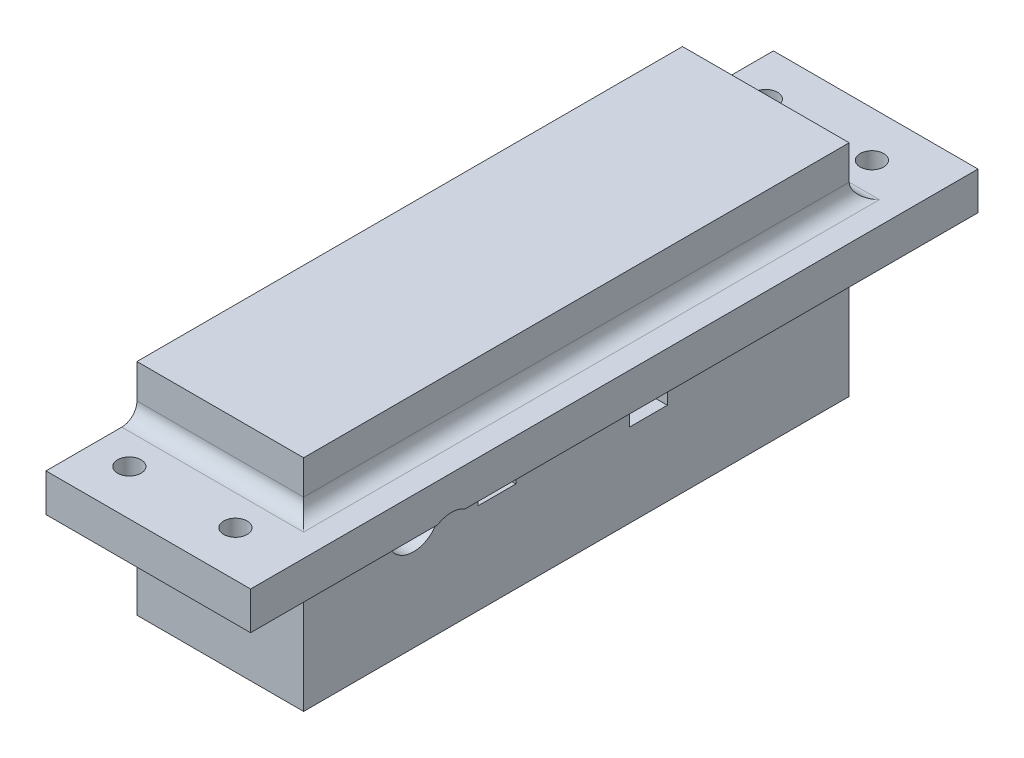
SolidWorks part; units mm, degrees
ref_plane "前基準面" through (0, 0, 0) normal (0, 0, 1) x (1, 0, 0)
ref_plane "上基準面" through (0, 0, 0) normal (0, 1, 0) x (1, 0, 0)
ref_plane "右基準面" through (0, 0, 0) normal (1, 0, 0) x (0, 0, -1)
sketch "草圖1" plane through (0, 0, 0) normal (1, 0, 0) x (0, 0, -1)
  line L1 (-30, 11.5) -> (33, 11.5)
  line L2 (-33, 8.5) -> (-33, -8.5)
  line L3 (-30, -11.5) -> (33, -11.5)
  line L4 (33, 11.5) -> (33, -11.5)
  line L5 (-33, 11.5) -> (33, -11.5) construction
  line L6 (-33, -11.5) -> (33, 11.5) construction
  line L7 (-36, 14.5) -> (36, 14.5)
  line L8 (-36, 14.5) -> (-36, -14.5)
  line L9 (-36, -14.5) -> (36, -14.5)
  line L10 (36, 14.5) -> (36, -14.5)
  line L11 (-36, 14.5) -> (36, -14.5) construction
  line L12 (-36, -14.5) -> (36, 14.5) construction
  arc A0 (-33, -8.5) -> (-30, -11.5) centre (-30, -8.5) ccw
  arc A1 (-30, 11.5) -> (-33, 8.5) centre (-30, 8.5) ccw
  point P0 (0, 0)
  point P6 (0, 0)
  dimension "D5" = 3
  dimension "D1" = 23
  dimension "D2" = 66
  dimension "D3" = 3
  dimension "D4" = 3
extrude "填料-伸長1" add sketch "草圖1" along normal blind 20
sketch "草圖2" plane through (0, 0, 36) normal (0, 0, 1) x (1, 0, 0)
  line L0 (0, 0) -> (20, 0) construction
  line L1 (0, 14.5) -> (0, -14.5) construction
  line L2 (20, 14.5) -> (20, -14.5) construction
  line L4 (0, 3) -> (11, 3)
  line L5 (0, 3) -> (0, -3)
  line L6 (0, -3) -> (11, -3)
  line L7 (11, 3) -> (11, -3)
  dimension "D1" = 11
  dimension "D2" = 3
  dimension "D3" = 3
extrude "除料-伸長1" cut sketch "草圖2" against normal up to next
sketch "草圖3" plane through (0, 0, -36) normal (0, 0, -1) x (-1, 0, 0)
  line L0 (0, 0) -> (-20, 0) construction
  line L1 (0, -14.5) -> (0, 14.5) construction
  line L2 (-20, -14.5) -> (-20, 14.5) construction
  circle A0 centre (-10, 0) radius 1.5
  dimension "D1" = 3
extrude "除料-伸長2" cut sketch "草圖3" against normal up to next
sketch "草圖4" plane through (20, 0, 0) normal (1, 0, 0) x (0, 0, -1)
  line L0 (-36, -14.5) -> (36, -14.5) construction
  line L1 (-36, 14.5) -> (36, 14.5)
  line L2 (-36, 14.5) -> (-36, -14.5)
  line L3 (-36, -14.5) -> (36, -14.5)
  line L4 (36, 14.5) -> (36, -14.5)
  line L5 (0, 0) -> (-36, 0) construction
  line L6 (-25, 3.5) -> (-18, 3.5) construction
  line L7 (-25, 3.5) -> (-25, -3.5) construction
  line L8 (-25, -3.5) -> (-18, -3.5) construction
  line L9 (-18, 3.5) -> (-18, -3.5) construction
  line L10 (-25, 3.5) -> (-18, -3.5) construction
  line L11 (-25, -3.5) -> (-18, 3.5) construction
  line L14 (36, -14.5) -> (36, 14.5) construction
  line L15 (-33, 8.5) -> (-33, -8.5) construction
  line L16 (-13, 2.5) -> (-8, 2.5)
  line L17 (-13, 2.5) -> (-13, -2.5)
  line L18 (-13, -2.5) -> (-8, -2.5)
  line L19 (-8, 2.5) -> (-8, -2.5)
  line L20 (-13, 2.5) -> (-8, -2.5) construction
  line L21 (-13, -2.5) -> (-8, 2.5) construction
  line L22 (0, 0) -> (36, 0) construction
  line L23 (7, 3.5) -> (12, 3.5)
  line L24 (7, 3.5) -> (7, -3.5)
  line L25 (7, -3.5) -> (12, -3.5)
  line L26 (12, 3.5) -> (12, -3.5)
  line L27 (7, 3.5) -> (12, -3.5) construction
  line L28 (7, -3.5) -> (12, 3.5) construction
  circle A1 centre (-21.5, 0) radius 3.5
  point P7 (-21.5, 0)
  point P18 (-10.5, 0)
  point P24 (9.5, 0)
  dimension "D1" = 25
  dimension "D2" = 15
  dimension "D3" = 7
  dimension "D4" = 7
  dimension "D5" = 5
  dimension "D6" = 5
  dimension "D7" = 45
  dimension "D8" = 40
  dimension "D9" = 7
extrude "填料-伸長2" add sketch "草圖4" along normal blind 2
sketch "草圖6" plane through (0, 0, 36) normal (0, 0, 1) x (1, 0, 0)
  line L0 (0, 14.5) -> (0, 3) construction
  line L1 (0, 8) -> (22, 8)
  line L2 (0, 8) -> (0, 3)
  line L3 (0, 3) -> (22, 3)
  line L4 (22, 8) -> (22, 3)
  line L5 (22, 14.5) -> (22, -14.5) construction
  line L6 (11, 3) -> (0, 3) construction
  dimension "D1" = 5
extrude "填料-伸長3" add sketch "草圖6" along normal blind 12
sketch "草圖7" plane through (0, 0, -36) normal (0, 0, -1) x (-1, 0, 0)
  line L0 (-22, -14.5) -> (-22, 14.5) construction
  line L1 (-22, 8) -> (0, 8)
  line L2 (-22, 8) -> (-22, 3)
  line L3 (-22, 3) -> (0, 3)
  line L4 (0, 8) -> (0, 3)
  line L5 (0, -14.5) -> (0, 14.5) construction
  line L6 (-22, 14.5) -> (0, 14.5) construction
  dimension "D1" = 5
  dimension "D2" = 11.5
extrude "填料-伸長4" add sketch "草圖7" along normal blind 12
sketch "草圖9" plane through (22, 0, 0) normal (1, 0, 0) x (0, 0, -1)
  line L0 (48, 8) -> (36, 8) construction
  line L1 (-48, 3) -> (-23.3028, 3)
  line L2 (-48, 3) -> (-48, 8)
  line L3 (-48, 8) -> (48, 8)
  line L4 (48, 3) -> (48, 8)
  line L6 (-19.6972, 3) -> (48, 3)
  line L7 (-48, 3) -> (-48, 8) construction
  line L8 (48, 8) -> (48, 3) construction
  circle A0 centre (-21.5, 0) radius 3.5 construction
  arc A1 (-19.6972, 3) -> (-23.3028, 3) centre (-21.5, 0) ccw
extrude "填料-伸長5" add sketch "草圖9" along normal blind 5
sketch "草圖10" plane through (0, 8, 0) normal (0, 1, 0) x (1, 0, 0)
  line L0 (0, -42) -> (27, -42) construction
  line L1 (0, -48) -> (0, -36) construction
  line L2 (27, 48) -> (27, -48) construction
  line L3 (0, 0) -> (27, 0) construction
  circle A0 centre (5, -42) radius 1.55
  circle A1 centre (19, -42) radius 1.55
  circle A2 centre (19, 42) radius 1.55
  circle A3 centre (5, 42) radius 1.55
  dimension "D1" = 3.1
  dimension "D2" = 3.1
  dimension "D3" = 5
  dimension "D4" = 8
extrude "除料-伸長4" cut sketch "草圖10" against normal up to next
fillet "圓角1" radius 2 3 edges at (11, 8, 36) (11, 8, -36) (22, 8, 0)
